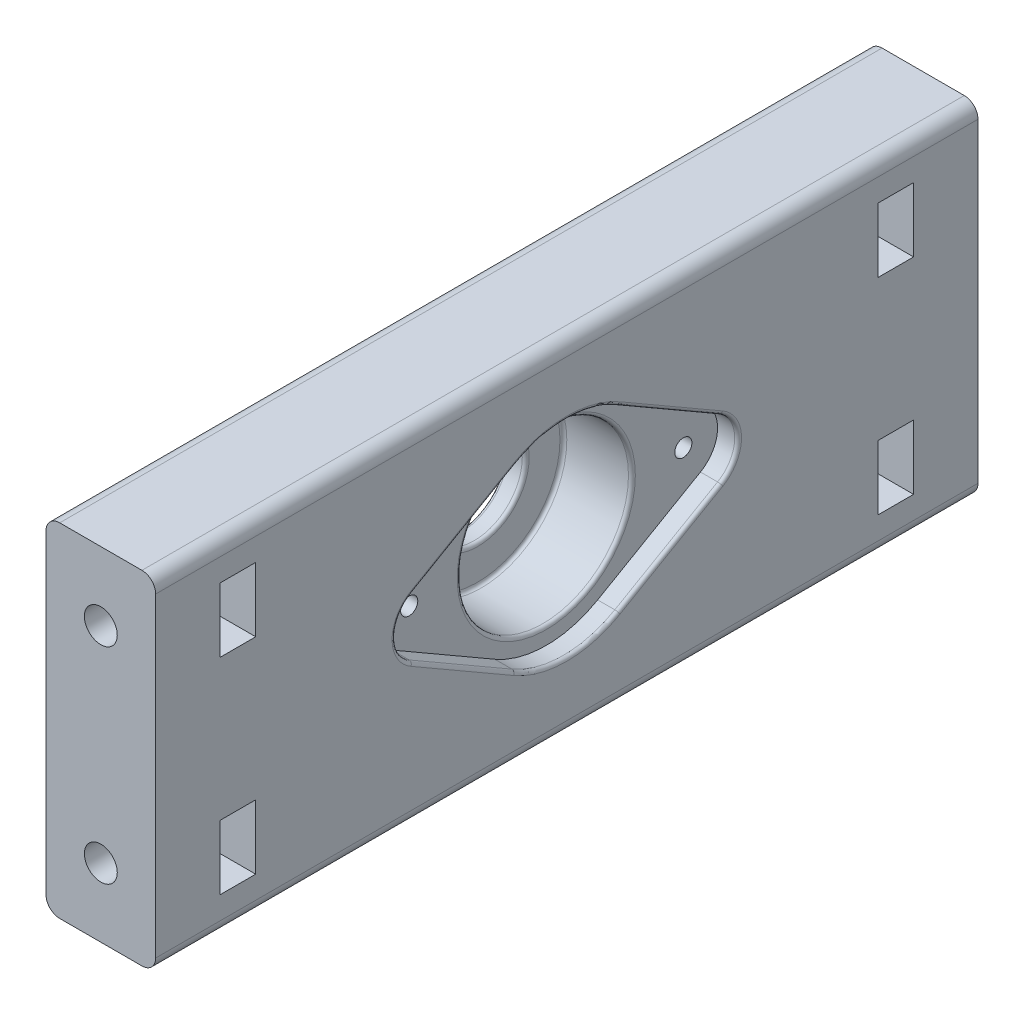
SolidWorks part; units mm, degrees
other "Markup1"
sketch "Sketch17" plane through (40, 40, -60) normal (0.6706, 0.1026, -0.7347) x (-0.7381, -0.0065, -0.6746)
ref_plane "Front Plane" through (0, 0, 0) normal (0, 0, 1) x (1, 0, 0)
ref_plane "Top Plane" through (0, 0, 0) normal (0, 1, 0) x (1, 0, 0)
ref_plane "Right Plane" through (0, 0, 0) normal (1, 0, 0) x (0, 0, -1)
ref_plane "Plane1" through (0, 0, 60) normal (0, 0, 1) x (1, 0, 0)
sketch "Sketch2" plane through (0, 0, 60) normal (0, 0, 1) x (1, 0, 0)
  line L2 (0, -60) -> (0, 0) construction
  line L3 (-39.322, -7.3333) -> (-28.5085, -65.3167)
  line L4 (39.322, -7.3333) -> (28.5085, -65.3167)
  circle A0 centre (0, 0) radius 30 construction
  arc A1 (39.322, -7.3333) -> (-39.322, -7.3333) centre (0, 0) ccw
  circle A2 centre (0, -60) radius 24 construction
  arc A3 (-28.5085, -65.3167) -> (28.5085, -65.3167) centre (0, -60) ccw
  circle A4 centre (0, 0) radius 12.5
  circle A5 centre (0, -60) radius 12.5 construction
  dimension "D1" = 60
  dimension "D2" = 10
  dimension "D5" = 48
  dimension "D6" = 5
  dimension "D7" = 25
  dimension "D8" = 25
  dimension "D3" = 60
extrude "Boss-Extrude1" add sketch "Sketch2" against normal blind 15
sketch "Sketch13" plane through (0, 0, 45) normal (0, 0, -1) x (-1, 0, 0)
  line L0 (0, 0) -> (0, -60) construction
  line L2 (13, -74) -> (-3, -74)
  line L3 (13, -74) -> (13, -24)
  line L4 (13, -24) -> (-3, -24)
  line L5 (-3, -74) -> (-3, -24)
  line L6 (13, -74) -> (-3, -24) construction
  line L7 (13, -24) -> (-3, -74) construction
  point P9 (5, -49)
  dimension "D1" = 16
  dimension "D2" = 50
  dimension "D3" = 11
  dimension "D4" = 5
extrude "Boss-Extrude5" add sketch "Sketch13" along normal up to surface (45 mm away) up to plane "Front Plane"
mirror "Mirror2" about plane through (0, 0, 0) normal (0, 0, 1) of "Boss-Extrude1", "Boss-Extrude5"
mirror "Mirror4" about plane through (0, 0, 0) normal (0, 0, 1) of "Boss-Extrude1"
sketch "Sketch5" plane through (0, 0, 0) normal (0, 0, 1) x (1, 0, 0)
  point P0 (0, 0)
sketch "Sketch14" plane through (3, 0, 0) normal (1, 0, 0) x (0, 0, -1)
  line L0 (45, -24) -> (-45, -24) construction
  circle A0 centre (0, -49) radius 12.5
  dimension "D1" = 25
  dimension "D2" = 25
extrude "Cut-Extrude1" cut sketch "Sketch14" against normal blind 13
sketch "Sketch15" plane through (3, 0, 0) normal (1, 0, 0) x (0, 0, -1)
  line L0 (-22.5, -44.6699) -> (-7.5, -36.0096)
  line L1 (7.5, -36.0096) -> (22.5, -44.6699)
  line L2 (-22.5, -53.3301) -> (-7.5, -61.9904)
  line L3 (7.5, -61.9904) -> (22.5, -53.3301)
  arc A0 (-7.5, -61.9904) -> (7.5, -61.9904) centre (0, -49) ccw
  circle A1 centre (20, -49) radius 1.25
  circle A2 centre (-20, -49) radius 1.25
  arc A3 (-22.5, -44.6699) -> (-22.5, -53.3301) centre (-20, -49) ccw
  arc A4 (22.5, -53.3301) -> (22.5, -44.6699) centre (20, -49) ccw
  arc A5 (7.5, -36.0096) -> (-7.5, -36.0096) centre (0, -49) ccw
  dimension "D1" = 30
  dimension "D2" = 2.5
  dimension "D3" = 20
  dimension "D4" = 20
extrude "Cut-Extrude2" cut sketch "Sketch15" against normal blind 3
sketch "Sketch16" plane through (3, 0, 0) normal (1, 0, 0) x (0, 0, -1)
  circle A0 centre (0, -49) radius 7
  circle A5 centre (20, -49) radius 1.25 construction
  circle A6 centre (-20, -49) radius 1.25 construction
  circle A7 centre (20, -49) radius 1.25
  circle A8 centre (-20, -49) radius 1.25
  dimension "D3" = 14
extrude "Cut-Extrude3" cut sketch "Sketch16" against normal through all
fillet "Fillet3" radius 0.5 3 edges at (-10, -49, -7) (0, -49, -12.5) (-10, -49, -12.5)
fillet "Fillet4" radius 0.5 1 edges at (-13, -49, -7)
fillet "Fillet5" radius 0.5 8 edges at (3, -34, 0) (3, -40.3397, -15) (3, -49, -25) (3, -57.6603, -15) (3, -64, 0) (3, -57.6603, 15) (3, -49, 25) (3, -40.3397, 15)
sketch "Sketch18" plane through (0, 0, 0) normal (0, 0, 1) x (1, 0, 0)
  line L0 (0, 0) -> (0, -49) construction
  line L1 (0, -49) -> (60, -49) construction
  line L2 (60, -49) -> (0, 0) construction
  dimension "D1" = 49
  dimension "D2" = 60
sketch "Sketch21" plane through (0, 0, 45) normal (0, 0, -1) x (-1, 0, 0)
  line L0 (0, 0) -> (0, -49) construction
  line L1 (0, -49) -> (-44.2154, -49) construction
  line L2 (-44.2154, -49) -> (0, 0) construction
  line L5 (-63.9491, -39.2748) -> (-35.8795, 17.6822)
  line L6 (-52.7436, -69.2798) -> (-11.2417, -86.7324)
  line L7 (-39.322, -7.3333) -> (-28.5085, -65.3167)
  line L8 (39.322, -7.3333) -> (32.1833, -45.612)
  line L9 (52.7436, -69.2798) -> (11.2417, -86.7324)
  line L10 (63.9491, -39.2748) -> (35.8795, 17.6822)
  line L11 (31.7709, -47.8233) -> (28.5085, -65.3167)
  line L12 (35.8795, 17.6822) -> (11.2417, -86.7324)
  circle A0 centre (0, 0) radius 44 construction
  arc A1 (-63.9491, -39.2748) -> (-52.7436, -69.2798) centre (-44.2154, -49) ccw
  arc A2 (-28.5085, -65.3167) -> (28.5085, -65.3167) centre (0, -60) ccw construction
  arc A3 (39.322, -7.3333) -> (-39.322, -7.3333) centre (0, 0) ccw construction
  arc A4 (-11.2417, -86.7324) -> (28.5085, -65.3167) centre (0, -60) ccw
  arc A5 (39.322, -7.3333) -> (-35.8795, 17.6822) centre (0, 0) ccw
  arc A6 (-35.8795, 17.6822) -> (-39.322, -7.3333) centre (0, 0) ccw
  arc A7 (-11.2417, -86.7324) -> (-28.5085, -65.3167) centre (0, -60) cw
  circle A8 centre (-44.2154, -49) radius 12.5
  arc A9 (11.2417, -86.7324) -> (28.5085, -65.3167) centre (0, -60) ccw
  arc A10 (35.8795, 17.6822) -> (39.322, -7.3333) centre (0, 0) cw
  arc A11 (63.9491, -39.2748) -> (52.7436, -69.2798) centre (44.2154, -49) cw
  circle A12 centre (44.2154, -49) radius 12.5
  arc M4 (39.322, -7.3333) -> (-39.322, -7.3333) centre (0, 0) ccw
  arc M6 (-28.5085, -65.3167) -> (28.5085, -65.3167) centre (0, -60) ccw
  line M7 (28.5085, -65.3167) -> (39.322, -7.3333)
  dimension "D2" = 88
  dimension "D3" = 44
  dimension "D4" = 25
  dimension "D1" = 66
extrude "Boss-Extrude7" add sketch "Sketch21" against normal blind 15 contours A12 L9 A11 L10 M7 M6 M4 | A12 L12 M7 M4 M6
sketch "Sketch23" plane through (0, 0, 45) normal (0, 0, -1) x (-1, 0, 0)
  arc A1 (52.7436, -69.2798) -> (63.9491, -39.2748) centre (44.2154, -49) ccw construction
  circle A4 centre (44.2154, -49) radius 12.5
  circle A5 centre (44.2154, -49) radius 22
  dimension "D2" = 25
extrude "Boss-Extrude8" add sketch "Sketch23" along normal blind 10
sketch "Sketch24" plane through (0, 0, 35) normal (0, 0, -1) x (-1, 0, 0)
  circle A0 centre (44.2154, -49) radius 12.5
extrude "Cut-Extrude4" cut sketch "Sketch24" against normal through all
sketch "Sketch25" plane through (0, 0, 35) normal (0, 0, -1) x (-1, 0, 0)
  circle A0 centre (44.2154, -49) radius 12.5
  circle A1 centre (44.2154, -49) radius 7
  dimension "D1" = 14
  dimension "D2" = 25
extrude "Boss-Extrude9" add sketch "Sketch25" against normal blind 2
sketch "Sketch26" plane through (0, 0, 60) normal (0, 0, 1) x (1, 0, 0)
  line L0 (-51.0558, -30.2061) -> (-37.375, -67.7939) construction
  line L1 (-44.2154, -49) -> (-29.2154, -49) construction
  line L2 (-34.5736, -37.5093) -> (-47.8418, -26.3759)
  line L3 (-55.9798, -29.3379) -> (-58.9875, -46.3953)
  line L4 (-29.4433, -51.6047) -> (-32.4509, -68.6621)
  line L5 (-53.8572, -60.4907) -> (-40.5889, -71.6241)
  arc A0 (-58.9875, -46.3953) -> (-53.8572, -60.4907) centre (-44.2154, -49) ccw
  arc A1 (-40.5889, -71.6241) -> (-32.4509, -68.6621) centre (-37.375, -67.7939) ccw
  arc A2 (-47.8418, -26.3759) -> (-55.9798, -29.3379) centre (-51.0558, -30.2061) ccw
  arc A3 (-29.4433, -51.6047) -> (-34.5736, -37.5093) centre (-44.2154, -49) ccw
  point P5 (-44.2154, -49)
  dimension "D1" = 30
  dimension "D2" = 40
  dimension "D3" = 110
extrude "Cut-Extrude5" cut sketch "Sketch26" against normal blind 3
sketch "Sketch27" plane through (0, 0, 57) normal (0, 0, 1) x (1, 0, 0)
  circle A0 centre (-51.0558, -30.2061) radius 1.15
  circle A1 centre (-37.375, -67.7939) radius 1.15
  dimension "D1" = 2.3
  dimension "D2" = 2.3
extrude "Cut-Extrude6" cut sketch "Sketch27" against normal blind 8
mirror "Mirror12" about plane through (0, 0, 0) normal (0, 0, 1) of "Cut-Extrude6", "Boss-Extrude9", "Cut-Extrude5", "Cut-Extrude4", "Boss-Extrude8", "Boss-Extrude7"
sketch "Sketch28" plane through (0, 0, 45) normal (0, 0, -1) x (-1, 0, 0)
  circle A0 centre (0, 0) radius 20
  dimension "D1" = 40
extrude "Boss-Extrude10" add sketch "Sketch28" against normal blind 2
sketch "Sketch29" plane through (0, 0, 45) normal (0, 0, -1) x (-1, 0, 0)
  line L0 (-20, 0) -> (20, 0)
  arc A0 (-20, 0) -> (20, 0) centre (0, 0) ccw
  dimension "D1" = 40
extrude "Boss-Extrude11" add sketch "Sketch29" along normal blind 20
sketch "Sketch30" plane through (0, 0, 25) normal (0, 0, -1) x (-1, 0, 0)
  line L0 (20, 0) -> (-20, 0) construction
  circle A0 centre (0, 0) radius 5
  dimension "D1" = 10
extrude "Cut-Extrude7" cut sketch "Sketch30" against normal blind 10
sketch "Sketch31" plane through (0, 0, 0) normal (0, 1, 0) x (1, 0, 0)
  line L0 (-20, -25) -> (-5, -25) construction
  line L1 (-12.5, -25) -> (12.5, -25)
  line L2 (-12.5, -25) -> (-12.5, -35) construction
  line L3 (-12.5, -35) -> (12.5, -35) construction
  line L4 (12.5, -25) -> (12.5, -35) construction
  line L6 (5, -25) -> (20, -25) construction
  line L8 (5, -35) -> (-5, -35) construction
  circle A0 centre (12.5, -35) radius 1.9
  circle A1 centre (-12.5, -35) radius 1.9
  point P8 (12.5, -25)
  dimension "D2" = 3.8
  dimension "D3" = 3.8
extrude "Cut-Extrude8" cut sketch "Sketch31" against normal blind 12 contours A1 | A0
sketch "Sketch32" plane through (-30.9224, 58.3079, 60) normal (0, 0, 1) x (0.342, 0.9397, 0)
  line L0 (-51.0558, -30.2061) -> (-37.375, -67.7939) construction
  line L1 (-44.2154, -49) -> (-29.2154, -49) construction
  line L2 (-34.5736, -37.5093) -> (-47.8418, -26.3759)
  line L3 (-55.9798, -29.3379) -> (-58.9875, -46.3953)
  line L4 (-29.4433, -51.6047) -> (-32.4509, -68.6621)
  line L5 (-53.8572, -60.4907) -> (-40.5889, -71.6241)
  line L6 (-90.2603, -65.759) -> (-69.7391, -122.1405) construction
  arc A0 (-58.9875, -46.3953) -> (-53.8572, -60.4907) centre (-44.2154, -49) ccw
  arc A1 (-40.5889, -71.6241) -> (-32.4509, -68.6621) centre (-37.375, -67.7939) ccw
  arc A2 (-47.8418, -26.3759) -> (-55.9798, -29.3379) centre (-51.0558, -30.2061) ccw
  arc A3 (-29.4433, -51.6047) -> (-34.5736, -37.5093) centre (-44.2154, -49) ccw
  circle A4 centre (-44.2154, -49) radius 12.5 construction
extrude "Cut-Extrude9" cut sketch "Sketch32" against normal blind 3
sketch "Sketch33" plane through (0, 0, 57) normal (0, 0, 1) x (1, 0, 0)
  circle A0 centre (20, 0) radius 1.15
  circle A1 centre (-20, 0) radius 1.15
  dimension "D1" = 2.3
extrude "Cut-Extrude10" cut sketch "Sketch33" against normal blind 8
mirror "Mirror13" about plane through (0, 0, 0) normal (0, 0, 1) of "Boss-Extrude11", "Cut-Extrude7", "Cut-Extrude8", "Cut-Extrude9", "Cut-Extrude10", "Boss-Extrude10"
fillet "Fillet6" radius 1 22 edges at (-31.9927, -78.0061, -45) (-31.9927, -78.0061, -60) (13.7548, -85.5305, -45) (13.7548, -85.5305, -60) (-49.9143, -10.7963, -45) (-49.9143, -10.7963, -60) (12.6256, 37.9551, -45) (12.6256, 37.9551, -60) (-64.8251, -56.6968, -60) (-31.9927, -78.0061, 45) (-31.9927, -78.0061, 60) (13.7548, -85.5305, 60) (13.7548, -85.5305, 45) (-49.9143, -10.7963, 45) (-49.9143, -10.7963, 60) (12.6256, 37.9551, 60) (12.6256, 37.9551, 45) (-64.8251, -56.6968, 60) (33.9153, -36.325, -60) (33.9153, -36.325, -45) (33.9153, -36.325, 60) (33.9153, -36.325, 45)
fillet "Fillet7" radius 1 16 edges at (0, 0, -45) (0, 0, 45) (20, 0, -35) (-20, 0, -35) (0, -20, -25) (0, -20, -45) (-20, 0, 35) (20, 0, 35) (0, -20, 25) (0, -20, 45) (0, -5, -25) (0, -5, 25) (12.5, 0, 25) (-12.5, 0, 25) (-12.5, 0, -25) (12.5, 0, -25)
fillet "Fillet8" radius 2 4 edges at (-13, -74, 0) (3, -74, 0) (-13, -24, 0) (3, -24, 0)
fillet "Fillet9" radius 2 4 edges at (-51.2154, -49, -35) (-66.2154, -49, -35) (-51.2154, -49, 35) (-66.2154, -49, 35)
sketch "Sketch35" plane through (0, 0, 60) normal (0, 0, 1) x (1, 0, 0)
  line L0 (-5, -49) -> (-5, -34) construction
  line L1 (-5, -49) -> (-5, -64) construction
  line L2 (-13, -24) -> (3, -74) construction
  line L3 (-13, -74) -> (3, -24) construction
  line L4 (-13, -74) -> (3, -74) construction
  line L5 (-13, -74) -> (-13, -24) construction
  line L6 (-13, -24) -> (3, -24) construction
  line L7 (3, -74) -> (3, -24) construction
  line L8 (-13, -24) -> (3, -74) construction
  line L9 (-13, -74) -> (3, -24) construction
  line L10 (-13, -74) -> (3, -74) construction
  line L11 (-13, -74) -> (-13, -24) construction
  line L12 (-13, -24) -> (3, -24) construction
  line L13 (3, -74) -> (3, -24) construction
  circle A0 centre (-5, -34) radius 2.4
  circle A1 centre (-5, -64) radius 2.4
  dimension "D2" = 4.8
  dimension "D3" = 4.8
  dimension "D1" = 10
extrude "Cut-Extrude12" cut sketch "Sketch35" against normal through all
sketch "Sketch38" plane through (0, 0, -45) normal (0, 0, 1) x (1, 0, 0)
  line L0 (-63.9491, -39.2748) -> (-35.8795, 17.6822) construction
  line L1 (-11.2417, -86.7324) -> (-52.7436, -69.2798) construction
  line L2 (39.322, -7.3333) -> (28.5085, -65.3167) construction
  line L3 (-63.9491, -39.2748) -> (-35.8795, 17.6822)
  line L4 (-11.2417, -86.7324) -> (-52.7436, -69.2798)
  line L5 (39.322, -7.3333) -> (28.5085, -65.3167)
  line L6 (1, -74) -> (-11, -74) construction
  line L7 (-13, -72) -> (-13, -26) construction
  line L8 (-11, -24) -> (1, -24) construction
  line L9 (3, -26) -> (3, -72) construction
  line L10 (1, -74) -> (-11, -74)
  line L11 (-13, -72) -> (-13, -26)
  line L12 (-11, -24) -> (1, -24)
  line L13 (3, -26) -> (3, -72)
  line L15 (-138.0147, -145.4375) -> (49.5839, -145.4375)
  line L16 (-138.0147, -145.4375) -> (-138.0147, 47.4375)
  line L17 (-138.0147, 47.4375) -> (49.5839, 47.4375)
  line L18 (49.5839, -145.4375) -> (49.5839, 47.4375)
  line L19 (-138.0147, -145.4375) -> (49.5839, 47.4375) construction
  line L20 (-138.0147, 47.4375) -> (49.5839, -145.4375) construction
  circle A0 centre (-44.2154, -49) radius 22 construction
  arc A1 (-11.2417, -86.7324) -> (28.5085, -65.3167) centre (0, -60) ccw construction
  arc A2 (39.322, -7.3333) -> (-35.8795, 17.6822) centre (0, 0) ccw construction
  circle A3 centre (-44.2154, -49) radius 22
  arc A4 (-11.2417, -86.7324) -> (28.5085, -65.3167) centre (0, -60) ccw
  arc A5 (39.322, -7.3333) -> (-35.8795, 17.6822) centre (0, 0) ccw
  arc A6 (-13, -72) -> (-11, -74) centre (-11, -72) ccw construction
  arc A7 (-11, -24) -> (-13, -26) centre (-11, -26) ccw construction
  arc A8 (1, -74) -> (3, -72) centre (1, -72) ccw construction
  arc A9 (3, -26) -> (1, -24) centre (1, -26) ccw construction
  arc A10 (-13, -72) -> (-11, -74) centre (-11, -72) ccw
  arc A11 (-11, -24) -> (-13, -26) centre (-11, -26) ccw
  arc A12 (1, -74) -> (3, -72) centre (1, -72) ccw
  arc A13 (3, -26) -> (1, -24) centre (1, -26) ccw
  arc M1 (-20.9709, -1.1053) -> (-18.9737, 1) centre (-18.9737, -1) cw
  line M2 (-18.9737, 1) -> (18.9737, 1)
  arc M3 (18.9737, 1) -> (20.9709, -1.1053) centre (18.9737, -1) cw
  arc M4 (20.9709, -1.1053) -> (-20.9709, -1.1053) centre (0, 0) cw
  arc M5 (-60.1534, -33.8349) -> (-46.3112, -70.8999) centre (-44.2154, -49) cw
  line M6 (-46.3112, -70.8999) -> (-10.8541, -85.8106)
  arc M7 (-10.8541, -85.8106) -> (27.5254, -65.1333) centre (0, -60) ccw
  line M8 (27.5254, -65.1333) -> (38.339, -7.15)
  arc M9 (38.339, -7.15) -> (-34.9825, 17.2401) centre (0, 0) ccw
  line M10 (-34.9825, 17.2401) -> (-60.1534, -33.8349)
  line M11 (-13, -72) -> (-13, -26)
  arc M12 (-13, -26) -> (-11, -24) centre (-11, -26) cw
  line M13 (-11, -24) -> (1, -24)
  arc M14 (1, -24) -> (3, -26) centre (1, -26) cw
  line M15 (3, -26) -> (3, -72)
  arc M16 (3, -72) -> (1, -74) centre (1, -72) cw
  line M17 (1, -74) -> (-11, -74)
  arc M18 (-11, -74) -> (-13, -72) centre (-11, -72) cw
extrude "Cut-Extrude15" cut sketch "Sketch38" against normal through all contours M10 M5 M6 M7 M8 M9 M18 M11 M12 M13 M14 M15 M16 M17 M4 M1 M2 M3
sketch "Sketch41" plane through (0, 0, 45) normal (0, 0, -1) x (-1, 0, 0)
  line L1 (-82.7232, 92.6987) -> (82.7232, 92.6987)
  line L2 (-82.7232, 92.6987) -> (-82.7232, -92.6987)
  line L3 (-82.7232, -92.6987) -> (82.7232, -92.6987)
  line L4 (13, -72) -> (13, -26)
  line L5 (11, -24) -> (-1, -24)
  line L6 (-3, -26) -> (-3, -72)
  line L7 (-1, -74) -> (11, -74)
  line L8 (13, -72) -> (13, -26)
  line L9 (11, -24) -> (-1, -24)
  line L10 (-3, -26) -> (-3, -72)
  line L11 (-1, -74) -> (11, -74)
  line L12 (82.7232, 92.6987) -> (82.7232, -92.6987)
  line L13 (-82.7232, 92.6987) -> (82.7232, -92.6987) construction
  line L14 (-82.7232, -92.6987) -> (82.7232, 92.6987) construction
  arc A4 (11, -74) -> (13, -72) centre (11, -72) ccw
  arc A5 (13, -26) -> (11, -24) centre (11, -26) ccw
  arc A6 (-1, -24) -> (-3, -26) centre (-1, -26) ccw
  arc A7 (-3, -72) -> (-1, -74) centre (-1, -72) ccw
  arc A8 (11, -74) -> (13, -72) centre (11, -72) ccw
  arc A9 (13, -26) -> (11, -24) centre (11, -26) ccw
  arc A10 (-1, -24) -> (-3, -26) centre (-1, -26) ccw
  arc A11 (-3, -72) -> (-1, -74) centre (-1, -72) ccw
  point P0 (0, 0)
  dimension "D1" = 0
extrude "Cut-Extrude16" cut sketch "Sketch41" against normal through all
sketch "Sketch42" plane through (0, 0, 0) normal (0, 0, 1) x (1, 0, 0)
  circle A0 centre (-5, -34) radius 2.4
  circle A1 centre (-5, -64) radius 2.4
extrude "Boss-Extrude12" add sketch "Sketch42" along normal mid plane 60
sketch "Sketch43" plane through (3, 0, 0) normal (1, 0, 0) x (0, 0, -1)
  line L0 (60, -66.4) -> (60, -61.6) construction
  line L1 (60, -36.4) -> (60, -31.6) construction
  line L2 (60, -66.4) -> (60, -61.6)
  line L3 (60, -36.4) -> (60, -31.6)
  line L4 (60, -26) -> (-60, -26)
  line L5 (-60, -26) -> (-60, -72)
  line L6 (-60, -72) -> (60, -72)
  line L7 (60, -72) -> (60, -26)
  line L8 (60, -26) -> (-60, -26)
  line L9 (-60, -26) -> (-60, -72)
  line L10 (-60, -72) -> (60, -72)
  line L11 (60, -72) -> (60, -26)
  line L12 (60, -34) -> (48, -34) construction
  dimension "D2" = 12
  dimension "D1" = 0
ref_plane "Plane2" through (0, 0, -48) normal (0, 0, -1) x (-1, 0, 0)
sketch "Sketch44" plane through (0, 0, -48) normal (0, 0, -1) x (-1, 0, 0)
  line L0 (2.2865, -29.3) -> (-3, -29.3)
  line L1 (10.4271, -34) -> (7.7135, -29.3)
  line L2 (7.7135, -29.3) -> (2.2865, -29.3)
  line L3 (2.2865, -29.3) -> (-0.4271, -34)
  line L4 (-0.4271, -34) -> (2.2865, -38.7)
  line L5 (2.2865, -38.7) -> (7.7135, -38.7)
  line L6 (7.7135, -38.7) -> (10.4271, -34)
  line L7 (-3, -26) -> (-3, -72) construction
  line L8 (2.2865, -38.7) -> (-3, -38.7)
  line L9 (-3, -38.7) -> (-3, -29.3)
  circle A0 centre (5, -64) radius 2.4 construction
  circle A1 centre (5, -34) radius 2.4 construction
  circle A2 centre (5, -64) radius 2.4
  circle A3 centre (5, -34) radius 2.4
  circle A4 centre (5, -34) radius 4.7 construction
  dimension "D1" = 9.4
extrude "Cut-Extrude17" cut sketch "Sketch44" along normal mid plane 5.2 contours L5 L6 L1 L2 L3 L4 A3 | L9 L8 L4 L3 L0
ref_plane "Plane3" through (0, -49, 0) normal (0, -1, 0) x (-1, 0, 0)
mirror "Mirror15" about plane through (0, -49, 0) normal (0, -1, 0) of "Cut-Extrude17"
mirror "Mirror16" about plane through (0, 0, 0) normal (0, 0, 1) of "Mirror15", "Cut-Extrude17"
